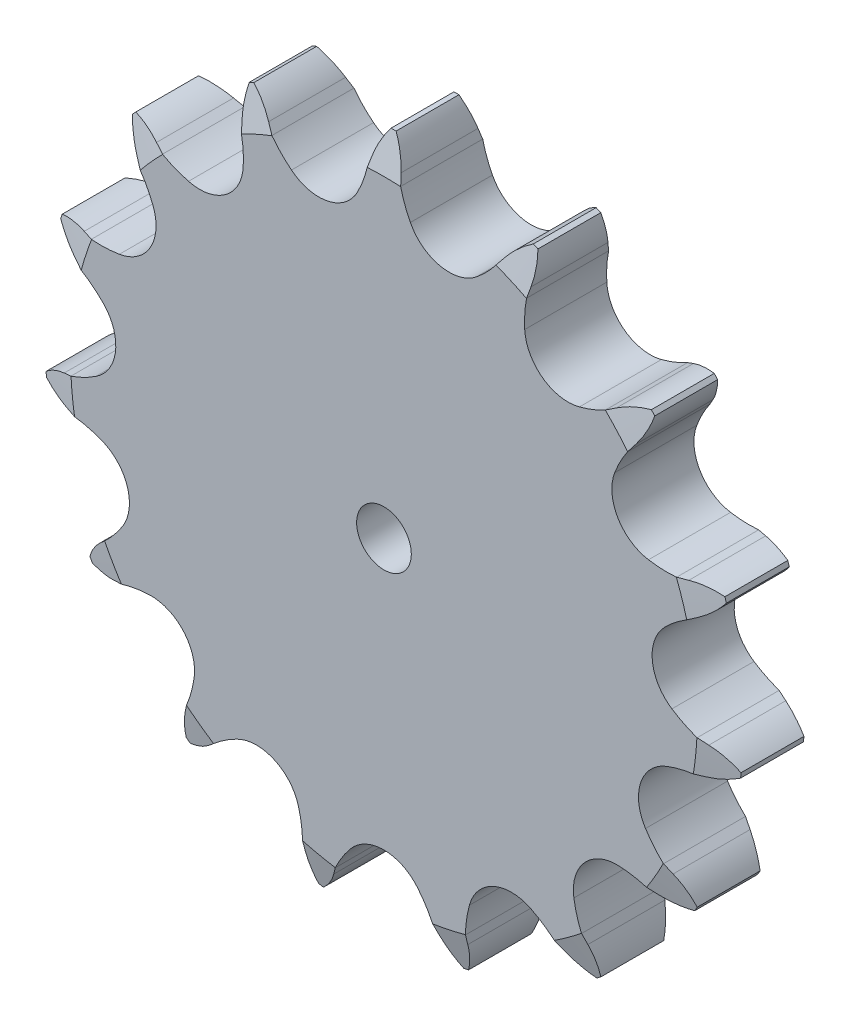
SolidWorks part; units mm, degrees
ref_plane "Front Plane" through (0, 0, 0) normal (0, 0, 1) x (1, 0, 0)
ref_plane "Top Plane" through (0, 0, 0) normal (0, 1, 0) x (1, 0, 0)
ref_plane "Right Plane" through (0, 0, 0) normal (1, 0, 0) x (0, 0, -1)
sketch "Sketch1" plane through (0, 0, 0) normal (0, 0, 1) x (1, 0, 0)
  line L3 (0, 0) -> (0, 54.4723) construction
  line L4 (-44.2979, 22.9064) -> (42.9505, 22.9064) construction
  line L5 (3.9479, 39.4826) -> (3.9479, 22.7186) construction
  line L6 (-19.6613, 26.1033) -> (20.7308, 26.1033) construction
  line L7 (3.9479, 26.1033) -> (-8.6727, 15.8833) construction
  line L8 (3.9479, 26.1033) -> (-3.5656, 22.6422) construction
  line L9 (-3.5656, 22.6422) -> (-6.4779, 28.9642) construction
  line L10 (-8.6957, 36.9773) -> (-8.6957, 20.618) construction
  line L11 (-19.962, 21.058) -> (23.9482, 21.058) construction
  line L12 (0, 0) -> (-9.3983, 44.2157) construction
  line L13 (-3.5656, 22.6422) -> (-3.8617, 23.2849) construction
  line L14 (3.5656, 22.6422) -> (3.8617, 23.2849) construction
  line L59 (0, 0) -> (0, -15) construction
  circle A0 centre (0, 0) radius 4 construction
  circle A2 centre (0, 0) radius 25.527 construction
  circle A8 centre (0, 0) radius 22.9064 construction
  circle A9 centre (0, 22.9064) radius 3.1781 construction
  arc A10 (-3.5656, 22.6422) -> (-2.4698, 20.9063) centre (3.9234, 26.1559) ccw construction
  circle A11 centre (-8.6957, 21.058) radius 5.3223 construction
  arc A12 (2.4698, 20.9063) -> (-2.4698, 20.9063) centre (0, 22.9064) cw construction
  arc A13 (-2.4698, 20.9063) -> (-3.5656, 22.6422) centre (3.9234, 26.1559) cw construction
  arc A14 (-3.8617, 23.2849) -> (-5.357, 25.2029) centre (-8.6957, 21.058) ccw construction
  arc A15 (2.4698, 20.9063) -> (3.5656, 22.6422) centre (-3.9234, 26.1559) ccw construction
  arc A16 (3.8617, 23.2849) -> (5.357, 25.2029) centre (8.6957, 21.058) cw construction
  arc A127 (-5.357, 25.2029) -> (5.357, 25.2029) centre (0, 22.9064) cw construction
  point P24 (3.9479, 26.1033)
  point P27 (0, 22.9064)
  point P38 (-5.357, 25.2029)
  point P339 (0, 0)
sketch "Sketch2" plane through (0, 0, 0) normal (1, 0, 0) x (0, 0, -1)
  line L1 (-3, 4) -> (3, 4) construction
  line L3 (-3, -25.527) -> (3, -25.527) construction
  line L4 (-3, 25.527) -> (3, 25.527) construction
  line L11 (-3, 0) -> (3, 0) construction
  point P4 (0, 4)
  point P6 (0, 25.527)
  point P10 (0, -25.527)
  point P14 (0, 0)
  dimension "O'all Width" = 6
sketch "Sketch3" plane through (0, 0, 0) normal (1, 0, 0) x (0, 0, -1)
  line L0 (-3, 25.527) -> (3, 25.527) construction
  line L1 (-3, 4) -> (3, 4)
  line L2 (-3, 4) -> (-3, 25.527)
  line L3 (-3, 25.527) -> (3, 25.527)
  line L4 (3, 4) -> (3, 25.527)
  line L5 (-3, 4) -> (3, 4) construction
  dimension "D1" = 21.527
revolve "Revolve5" add sketch "Sketch3" angle 360 about L11
sketch "Sketch4" plane through (0, 0, 0) normal (0, 0, 1) x (1, 0, 0)
  line L0 (-3.5656, 22.6422) -> (-3.8617, 23.2849) construction
  line L1 (1.2199, 22.8887) -> (1.0639, 23.5789)
  line L2 (-3.5656, 22.6422) -> (-3.8617, 23.2849) construction
  line L4 (3.5656, 22.6422) -> (3.8617, 23.2849) construction
  line L5 (3.5656, 22.6422) -> (3.8617, 23.2849) construction
  line L6 (0, 0) -> (0, 25.527) construction
  line L9 (8.1953, 21.4061) -> (8.6185, 21.9731)
  line L10 (0, 0) -> (4.7625, 22.4058) construction
  line L11 (0, 0) -> (-4.7625, 22.4058) construction
  arc A0 (-3.8617, 23.2849) -> (-5.357, 25.2029) centre (-8.6957, 21.058) ccw construction
  arc A1 (-3.5656, 22.6422) -> (-2.4698, 20.9063) centre (3.9234, 26.1559) ccw construction
  arc A2 (-2.4698, 20.9063) -> (2.4698, 20.9063) centre (0, 22.9064) ccw construction
  circle A3 centre (0, 0) radius 25.527 construction
  arc A6 (-3.8617, 23.2849) -> (-5.357, 25.2029) centre (-8.6957, 21.058) ccw construction
  arc A7 (-3.5656, 22.6422) -> (-2.4698, 20.9063) centre (3.9234, 26.1559) ccw construction
  arc A8 (-2.4698, 20.9063) -> (2.4698, 20.9063) centre (0, 22.9064) ccw construction
  arc A12 (2.4698, 20.9063) -> (3.5656, 22.6422) centre (-3.9234, 26.1559) ccw construction
  arc A13 (5.357, 25.2029) -> (3.8617, 23.2849) centre (8.6957, 21.058) ccw construction
  arc A14 (5.357, 25.2029) -> (-5.357, 25.2029) centre (0, 22.9064) ccw construction
  arc A15 (2.4698, 20.9063) -> (3.5656, 22.6422) centre (-3.9234, 26.1559) ccw construction
  arc A16 (5.357, 25.2029) -> (3.8617, 23.2849) centre (8.6957, 21.058) ccw construction
  arc A17 (5.357, 25.2029) -> (-5.357, 25.2029) centre (0, 22.9064) ccw construction
  arc A23 (10.48, 23.5384) -> (0, 25.766) centre (4.7625, 22.4058) ccw
  arc A24 (1.0639, 23.5789) -> (0, 25.766) centre (-4.1275, 22.4058) ccw
  arc A25 (1.2199, 22.8887) -> (1.9308, 20.963) centre (9.2758, 24.7686) ccw
  arc A26 (1.9308, 20.963) -> (6.7625, 19.936) centre (4.7625, 22.4058) ccw
  arc A27 (6.7625, 19.936) -> (8.1953, 21.4061) centre (1.6004, 26.4001) ccw
  arc A28 (10.48, 23.5384) -> (8.6185, 21.9731) centre (12.8839, 18.7899) ccw
  circle A29 centre (0, 0) radius 22.9064 construction
  circle A30 centre (0, 0) radius 28.7349 construction
  dimension "D2" = 12
  dimension "D4" = 24.733
  dimension "D5" = 24.733
  dimension "D1" = 12
  dimension "D3" = 2
extrude "Cut-Extrude4" cut sketch "Sketch4" against normal through all both and the other way through all
pattern_circular "CirPattern2" count 15 over 360 about axis through (0, 0, 3) along (0, 0, -1) of "Cut-Extrude4"
sketch "Sketch5" plane through (0, 0, 3) normal (0, 0, 1) x (1, 0, 0)
  circle A0 centre (0, 0) radius 22.9064 construction
  circle A1 centre (0, 0) radius 22.9064
extrude "Cut-Extrude5" cut sketch "Sketch5" against normal through all draft 75 flip side to cut
sketch "Sketch6" plane through (0, 0, -3) normal (0, 0, -1) x (-1, 0, 0)
  circle A1 centre (0, 0) radius 22.9064
  circle A2 centre (0, 0) radius 22.9064
  dimension "D1" = 0
extrude "Cut-Extrude6" cut sketch "Sketch6" against normal through all draft 75 flip side to cut
sketch "Sketch7" plane through (0, 0, 0) normal (0, 0, 1) x (1, 0, 0)
  point P0 (4.7625, 22.4058)
  point P1 (-4.7625, 22.4058)
ref_axis "Center Axis 1" through (0, 0, -3) along (0, 0, 1)
ref_axis "Center Axis 2" through (4.7625, 22.4058, -21.9306) along (0, 0, 1)
ref_axis "Center Axis 3" through (-4.7625, 22.4058, -22.0643) along (0, 0, 1)
sketch "Sketch8" plane through (0, 0, 3) normal (0, 0, 1) x (1, 0, 0)
  circle A0 centre (0, 0) radius 2
  circle A1 centre (0, 0) radius 4
  dimension "D1" = 4
  dimension "D2" = 8
extrude "Boss-Extrude1" add sketch "Sketch8" against normal up to surface (6 mm away) up to face at (0, -4, -3)
ref_plane "MIDPLANE" through (0, 0, 0) normal (0, 0, 1) x (1, 0, 0)
equation "\"D1@Sketch1\"=\"E@Sketch1\""
equation "\"No. of Teeth@CirPattern2\"=\"No. of Teeth@Sketch1\""
equation "\"D2@Sketch4\" =  ( 360 / \"No. of Teeth@Sketch1\" )  * .5"
equation "\"D5@Sketch4\" = \"D4@Sketch4\""
equation "\"D1@Sketch4\" = \"D2@Sketch4\""
